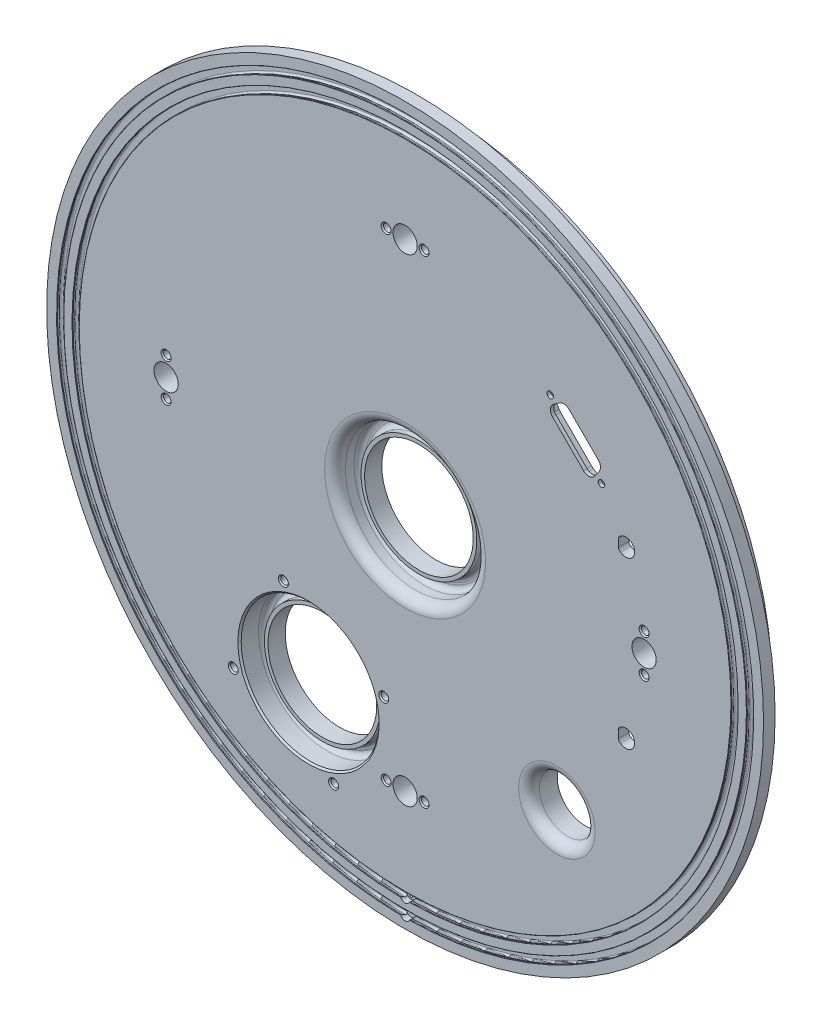
SolidWorks part; units mm, degrees
ref_plane "Front Plane" through (0, 0, 0) normal (0, 0, 1) x (1, 0, 0)
ref_plane "Top Plane" through (0, 0, 0) normal (0, 1, 0) x (1, 0, 0)
ref_plane "Right Plane" through (0, 0, 0) normal (1, 0, 0) x (0, 0, -1)
ref_axis "Axis1" through (0, 0, 87.1104) along (0, 0, -1)
sketch "Sketch1" plane through (0, 0, 0) normal (0, 0, 1) x (1, 0, 0)
  line L0 (-16.4103, -32.8206) -> (-28.0584, -56.1169) construction
  line L1 (-165.1, 165.1) -> (165.1, 165.1)
  line L2 (-165.1, 165.1) -> (-165.1, -165.1)
  line L3 (-165.1, -165.1) -> (165.1, -165.1)
  line L4 (165.1, 165.1) -> (165.1, -165.1)
  line L5 (0, -44.2246) -> (0, -100.8465) construction
  circle A0 centre (-44.45, -88.9) radius 25.4 construction
  circle A1 centre (0, 0) radius 25.4 construction
  circle A2 centre (69.85, -82.55) radius 11.7272 construction
  point P4 (165.1, 0)
  point P5 (0, 165.1)
  dimension "D3" = 50.8
  dimension "D4" = 50.8
  dimension "D5" = 44.45
  dimension "D9" = 69.85
  dimension "D1" = 330.2
  dimension "D2" = 330.2
  dimension "D6" = 88.9
  dimension "D7" = 26.565
  dimension "D8" = 82.55
extrude "BE-00 Material Blank" add sketch "Sketch1" against normal blind 15.875 and the other way blind 0.508
ref_plane "Plane1" through (-44.45, 0, 0) normal (1, 0, 0) x (0, 0, -1)
ref_plane "Plane2" through (69.85, 0, 0) normal (1, 0, 0) x (0, 0, -1)
sketch "Sketch5" plane through (0, 0, 0) normal (1, 0, 0) x (0, 0, -1)
  line L0 (0, 164.973) -> (0, 23.8125)
  line L1 (0, 23.8125) -> (14.3002, 23.8125)
  line L2 (-26.7351, 0) -> (-26.7351, 307.1876)
  line L3 (-26.7351, 307.1876) -> (49.4649, 307.1876)
  line L4 (49.4649, 307.1876) -> (49.4649, 0)
  line L5 (14.3002, 154.7876) -> (8.9662, 154.7876)
  line L6 (7.366, 156.3878) -> (7.366, 157.3895)
  line L7 (7.366, 157.3895) -> (5.334, 164.973)
  line L8 (5.334, 164.973) -> (0, 164.973)
  line L9 (60.1954, 0) -> (97.9061, 0) construction
  line L10 (14.3002, 154.7876) -> (14.3002, 23.8125)
  line L11 (-26.7351, 0) -> (49.4649, 0)
  arc A0 (8.9662, 154.7876) -> (7.366, 156.3878) centre (8.9662, 156.3878) cw
  dimension "D8" = 1.6002
  dimension "D1" = 15
  dimension "D2" = 7.366
  dimension "D3" = 5.334
  dimension "D4" = 309.5752
  dimension "D5" = 329.946
  dimension "D6" = 152.4
  dimension "D7" = 47.625
  dimension "D9" = 76.2
  dimension "D10" = 14.3002
revolve "CR-00 Profile Turn All" cut sketch "Sketch5" angle 360 about L9
sketch "Sketch18" plane through (0, 0, 0) normal (1, 0, 0) x (0, 0, -1)
  line L0 (-0.0254, 171.45) -> (-0.0254, 160.528)
  line L1 (-0.0254, 171.45) -> (-19.0148, 171.45)
  line L2 (-19.0148, 171.45) -> (-19.0148, 119.9486)
  line L3 (-19.0148, 119.9486) -> (-0.0254, 138.938)
  line L4 (0.3319, 160.296) -> (1.7371, 160.9216)
  line L5 (2.8448, 160.2023) -> (2.8448, 157.2977)
  line L6 (0.3319, 157.204) -> (1.7371, 156.5784)
  line L7 (-0.0254, 156.972) -> (-0.0254, 153.416)
  line L8 (0.3319, 153.184) -> (1.7371, 153.8096)
  line L9 (2.8448, 153.0903) -> (2.8448, 150.1857)
  line L10 (0.3319, 150.092) -> (1.7371, 149.4664)
  line L11 (-0.0254, 149.86) -> (-0.0254, 138.938)
  line L12 (2.8448, 158.75) -> (4.383, 158.75) construction
  line L13 (2.8448, 151.638) -> (4.383, 151.638) construction
  line L14 (0, 164.973) -> (0, 23.8125) construction
  line L15 (-94.6502, 0) -> (-55.4542, 0) construction
  arc A0 (-0.0254, 160.528) -> (0.3319, 160.296) centre (0.2286, 160.528) ccw
  arc A1 (2.8448, 160.2023) -> (1.7371, 160.9216) centre (2.0574, 160.2023) ccw
  arc A2 (2.8448, 157.2977) -> (1.7371, 156.5784) centre (2.0574, 157.2977) cw
  arc A3 (-0.0254, 156.972) -> (0.3319, 157.204) centre (0.2286, 156.972) cw
  arc A4 (-0.0254, 153.416) -> (0.3319, 153.184) centre (0.2286, 153.416) ccw
  arc A5 (2.8448, 153.0903) -> (1.7371, 153.8096) centre (2.0574, 153.0903) ccw
  arc A6 (2.8448, 150.1857) -> (1.7371, 149.4664) centre (2.0574, 150.1857) cw
  arc A7 (-0.0254, 149.86) -> (0.3319, 150.092) centre (0.2286, 149.86) cw
  point P37 (-0.0254, 160.1369)
  point P38 (-0.0254, 157.3631)
  point P39 (-0.0254, 145)
  dimension "D4" = 3.048
  dimension "D9" = 0.7874
  dimension "D10" = 0.254
  dimension "D14" = 4.4794
  dimension "D1" = 45
  dimension "D2" = 24
  dimension "D3" = 0.0254
  dimension "D5" = 7.112
  dimension "D6" = 12.7
  dimension "D7" = 12.7
  dimension "D8" = 18.9894
  dimension "D11" = 2.8448
  dimension "D12" = 317.5
  dimension "D13" = 2.7737
  dimension "D15" = 290
  dimension "D16" = 300.1841
revolve "CR-00 O-ring Grooves Radome" cut sketch "Sketch18" angle 360 about axis through (0, 0, 87.1104) along (0, 0, -1)
sketch "Sketch51" plane through (0, 0, 0) normal (0, 0, 1) x (1, 0, 0)
  circle A0 centre (0, -152.4) radius 2.1844
  circle A1 centre (0, -159.512) radius 2.1844
  dimension "D1" = 4.3688
  dimension "D2" = 159.512
  dimension "D3" = 7.112
extrude "Cut-Extrude6" cut sketch "Sketch51" against normal up to surface (2.8448 mm away) up to face at (153.0903, 0, -2.8448)
sketch "Sketch8" plane through (0, 0, 0) normal (0, 0, 1) x (1, 0, 0)
  circle A0 centre (-44.5452, -80.5824) radius 23.8125
  circle A1 centre (88.9, -44.45) radius 7.9375
  circle A2 centre (-88.9, -50.8) radius 11.1125
  dimension "D1" = 47.625
  dimension "D2" = 15.875
  dimension "D3" = 22.225
  dimension "D4" = 92.075
  dimension "D5" = 44.45
  dimension "D6" = 50.8
  dimension "D7" = 88.9
  dimension "D8" = 88.9
extrude "CE-00 Holes Vacuum Fittings" [suppressed] cut sketch "Sketch8" against normal through all
hole_wizard "1/2 NPT Tapped Hole1" positions "Sketch3" profile "Sketch4" size "1/2" standard "Ansi Inch"
sketch "Sketch3" plane through (-58.3455, -97.3945, -18.542) normal (0, 0, 1) x (1, 0, 0)
  point P0 (58.3455, 97.3945)
sketch "Sketch4" plane through (0, 0, -18.542) normal (1, 0, 0) x (0, 1, 0)
  line L0 (0, 0) -> (0, 19.05)
  line L1 (0, 19.05) -> (8.9281, 19.05)
  line L2 (-10.2617, 13.5636) -> (-10.6678, 0) construction
  line L3 (8.9281, 19.05) -> (8.9281, 13.5636)
  line L4 (8.9281, 13.5636) -> (10.2617, 13.5636)
  line L5 (10.2617, 13.5636) -> (10.6678, 0)
  line L7 (10.6678, 0) -> (0, 0)
  line L8 (0, -6.35) -> (0, 107.95) construction
  line L11 (-8.9281, 13.5636) -> (-10.2617, 13.5636) construction
  dimension "Thru Tap Drill Dia." = 17.8562
  dimension "Thru Tap Drill Depth" = 19.05
  dimension "Thread Dia." = 21.3355
  dimension "Thread Angle" = 3.43
  dimension "Thread Depth" = 13.5636
hole_wizard "#10-32 Tapped Hole1" positions "Sketch7" profile "Sketch6" tap size "#10-32" standard "Ansi Inch"
sketch "Sketch7" plane through (20.4721, 110.2727, -18.034) normal (0, 0, -1) x (-1, 0, 0)
  point P0 (58.5721, -110.2727)
  dimension "D1" = 38.1
sketch "Sketch6" plane through (-38.1, 0, -18.034) normal (1, 0, 0) x (0, 1, 0)
  line L0 (0, 0) -> (0, 17.0883)
  line L1 (0, 17.0883) -> (2.0193, 15.875)
  line L2 (2.0193, 15.875) -> (2.0193, 0.5207)
  line L3 (2.0193, 0.5207) -> (2.54, 0)
  line L5 (2.54, 0) -> (0, 0)
  line L6 (-2.0193, 0.5207) -> (-2.54, 0) construction
  line L10 (0, 17.0883) -> (-2.0193, 15.875) construction
  line L11 (0, -6.35) -> (0, 107.95) construction
  dimension "Tap Drill Dia." = 4.0386
  dimension "Tap Drill Depth" = 15.875
  dimension "Near C'Sink Dia." = 5.08
  dimension "Near C'Sink Angle" = 90
  dimension "Drill Angle" = 118
pattern_circular "CirPattern1" [suppressed] count 6 over 360 about axis through (0, 0, 87.1104) along (0, 0, -1)
hole_wizard "#10-32 Tapped Hole2" positions "Sketch10" profile "Sketch9" tap size "#10-32" standard "Ansi Inch"
sketch "Sketch10" plane through (0, 0, -18.034) normal (0, 0, -1) x (-1, 0, 0)
  point P0 (82.6452, -80.5824)
  dimension "D1" = 38.1
sketch "Sketch9" plane through (-82.6452, -80.5824, -18.034) normal (1, 0, 0) x (0, 1, 0)
  line L0 (0, 0) -> (0, 17.0883)
  line L1 (0, 17.0883) -> (2.0193, 15.875)
  line L2 (2.0193, 15.875) -> (2.0193, 0.5207)
  line L3 (2.0193, 0.5207) -> (2.54, 0)
  line L5 (2.54, 0) -> (0, 0)
  line L6 (-2.0193, 0.5207) -> (-2.54, 0) construction
  line L10 (0, 17.0883) -> (-2.0193, 15.875) construction
  line L11 (0, -6.35) -> (0, 107.95) construction
  dimension "Tap Drill Dia." = 4.0386
  dimension "Tap Drill Depth" = 15.875
  dimension "Near C'Sink Dia." = 5.08
  dimension "Near C'Sink Angle" = 90
  dimension "Drill Angle" = 118
pattern_circular "CirPattern2" [suppressed] count 6 over 360
hole_wizard "#8-32 Tapped Hole1" positions "Sketch12" profile "Sketch11" tap size "#8-32" standard "Ansi Inch"
sketch "Sketch12" plane through (0, 0, -18.034) normal (0, 0, -1) x (-1, 0, 0)
  point P0 (88.9, -28.575)
  dimension "D1" = 22.225
sketch "Sketch11" plane through (-88.9, -28.575, -18.034) normal (1, 0, 0) x (0, 1, 0)
  line L0 (0, 0) -> (0, 16.9128)
  line L1 (0, 16.9128) -> (1.7272, 15.875)
  line L2 (1.7272, 15.875) -> (1.7272, 0.5588)
  line L3 (1.7272, 0.5588) -> (2.286, 0)
  line L5 (2.286, 0) -> (0, 0)
  line L6 (-1.7272, 0.5588) -> (-2.286, 0) construction
  line L10 (0, 16.9128) -> (-1.7272, 15.875) construction
  line L11 (0, -6.35) -> (0, 107.95) construction
  dimension "Tap Drill Dia." = 3.4544
  dimension "Tap Drill Depth" = 15.875
  dimension "Near C'Sink Dia." = 4.572
  dimension "Near C'Sink Angle" = 90
  dimension "Drill Angle" = 118
pattern_circular "CirPattern3" [suppressed] count 6 over 360
hole_wizard "#8-32 Tapped Hole2" positions "Sketch14" profile "Sketch13" tap size "#8-32" standard "Ansi Inch"
sketch "Sketch14" plane through (0, 0, -18.034) normal (0, 0, -1) x (-1, 0, 0)
  point P0 (-88.9, -22.225)
  dimension "D1" = 22.225
sketch "Sketch13" plane through (88.9, -22.225, -18.034) normal (1, 0, 0) x (0, 1, 0)
  line L0 (0, 0) -> (0, 16.9128)
  line L1 (0, 16.9128) -> (1.7272, 15.875)
  line L2 (1.7272, 15.875) -> (1.7272, 0.5588)
  line L3 (1.7272, 0.5588) -> (2.286, 0)
  line L5 (2.286, 0) -> (0, 0)
  line L6 (-1.7272, 0.5588) -> (-2.286, 0) construction
  line L10 (0, 16.9128) -> (-1.7272, 15.875) construction
  line L11 (0, -6.35) -> (0, 107.95) construction
  dimension "Tap Drill Dia." = 3.4544
  dimension "Tap Drill Depth" = 15.875
  dimension "Near C'Sink Dia." = 4.572
  dimension "Near C'Sink Angle" = 90
  dimension "Drill Angle" = 118
pattern_circular "CirPattern4" [suppressed] count 6 over 360
sketch "Sketch29" plane through (0, 0, -14.3002) normal (0, 0, -1) x (-1, 0, 0)
  line L0 (0, -50.1457) -> (0, -101.6575) construction
  line L1 (13.7482, 109.5375) -> (16.0393, 113.5059)
  line L2 (-13.7482, 109.5375) -> (-16.0393, 113.5059)
  line L3 (-122.2502, -22.225) -> (-122.2502, -50.6266)
  line L4 (36.6551, 106.0023) -> (26.1856, 46.6263)
  line L5 (-11.4874, -104.0576) -> (10.6367, -68.097)
  line L6 (102.2177, 9.9539) -> (117.5706, 15.5419)
  line L8 (122.2502, -22.225) -> (122.2502, -62.5112)
  line L9 (-120.3903, 53.7153) -> (-67.4739, 106.6317)
  line L10 (-122.2502, 49.2252) -> (-122.2502, 22.225)
  line L11 (-55.441, 102.8378) -> (-40.4593, 17.872)
  line L12 (-88.4934, -87.6335) -> (-66.2507, -55.8677) construction
  line L13 (-117.5706, -15.5419) -> (-102.2177, -9.9539)
  line L14 (-32.0892, -40.2927) -> (-46.5225, -60.9056)
  line L15 (-63.958, -52.5933) -> (-41.6374, -20.7163)
  line L16 (99.7853, -9.525) -> (47.4632, -9.525)
  line L17 (88.4934, -87.6335) -> (41.6374, -20.7163)
  line L18 (122.2502, 49.2252) -> (122.2502, 22.225)
  line L19 (-102.2177, 9.9539) -> (-117.5706, 15.5419)
  line L20 (55.441, 102.8378) -> (40.4593, 17.872)
  line L21 (47.4632, 9.525) -> (99.7853, 9.525)
  line L22 (120.3903, 53.7153) -> (67.4739, 106.6317)
  line L23 (-36.6551, 106.0023) -> (-26.1856, 46.6263)
  line L24 (46.6891, -44.5372) -> (66.9379, -73.4555) construction
  line L25 (-12.674, -115.738) -> (-8.313, -127.7197)
  line L29 (-99.7853, -9.525) -> (-47.4632, -9.525)
  line L30 (117.5706, -15.5419) -> (102.2177, -9.9539)
  line L31 (-47.4632, 9.525) -> (-99.7853, 9.525)
  arc A0 (10.6367, -68.097) -> (29.0762, -52.2974) centre (44.45, -88.9) cw
  arc A1 (-15.8102, -137.2174) -> (-46.3064, -130.1318) centre (0, 0) cw
  arc A2 (22.2264, -38.494) -> (-22.6409, -38.2517) centre (0, 0) cw
  arc A3 (122.2502, 49.2252) -> (120.3903, 53.7153) centre (115.9002, 49.2252) ccw
  arc A4 (-122.2502, 49.2252) -> (-120.3903, 53.7153) centre (-115.9002, 49.2252) cw
  arc A5 (55.441, 102.8378) -> (67.4739, 106.6317) centre (62.445, 101.6028) cw
  arc A6 (102.2177, 9.9539) -> (99.7853, 9.525) centre (99.7853, 16.637) cw
  arc A7 (40.4593, 17.872) -> (47.4632, 9.525) centre (47.4632, 16.637) ccw
  arc A8 (-22.6409, -38.2517) -> (-32.0892, -40.2927) centre (-26.2634, -44.372) ccw
  arc A9 (-8.313, -127.7197) -> (-15.8102, -137.2174) centre (-14.9961, -130.1521) cw
  arc A10 (-115.0213, -76.4765) -> (-109.4209, -84.2949) centre (0, 0) ccw
  arc A11 (121.3884, -65.9046) -> (106.1569, -88.3701) centre (0, 0) cw
  arc A12 (29.0762, -52.2974) -> (22.2264, -38.494) centre (26.0866, -45.1797) ccw
  arc A13 (47.4632, -9.525) -> (41.6374, -20.7163) centre (47.4632, -16.637) ccw
  arc A14 (-26.1856, 46.6263) -> (-16.5359, 41.2598) centre (-19.1816, 47.8613) ccw
  arc A15 (-16.0393, 113.5059) -> (-36.6551, 106.0023) centre (-25.6857, 107.9365) ccw
  arc A16 (16.0393, 113.5059) -> (36.6551, 106.0023) centre (25.6857, 107.9365) cw
  arc A17 (16.5359, 41.2598) -> (26.1856, 46.6263) centre (19.1816, 47.8613) ccw
  arc A18 (-40.4593, 17.872) -> (-47.4632, 9.525) centre (-47.4632, 16.637) cw
  arc A19 (122.2502, 22.225) -> (117.5706, 15.5419) centre (115.1382, 22.225) cw
  arc A20 (-55.441, 102.8378) -> (-67.4739, 106.6317) centre (-62.445, 101.6028) ccw
  arc A21 (-50.9341, -122.2424) -> (-46.3064, -130.1318) centre (-43.9221, -123.4314) ccw
  arc A22 (122.2502, -22.225) -> (117.5706, -15.5419) centre (115.1382, -22.225) ccw
  arc A23 (-52.9134, -103.4798) -> (-46.7884, -68.6552) centre (-69.85, -82.55) ccw
  arc A24 (-69.7976, -55.6261) -> (-96.6956, -80.4969) centre (-69.85, -82.55) ccw
  arc A25 (-102.2177, -9.9539) -> (-99.7853, -9.525) centre (-99.7853, -16.637) cw
  arc A26 (-117.2181, -57.4276) -> (-122.2502, -50.6266) centre (-115.1382, -50.6266) cw
  arc A27 (-114.3694, -67.7636) -> (-115.0213, -76.4765) centre (-109.099, -72.5388) ccw
  arc A28 (-52.9134, -103.4798) -> (-53.5204, -113.9849) centre (-48.4396, -109.0084) ccw
  arc A29 (-69.7976, -55.6261) -> (-63.958, -52.5933) centre (-69.7838, -48.5141) ccw
  arc A30 (16.5359, 41.2598) -> (-16.5359, 41.2598) centre (0, 0) ccw
  arc A31 (122.2502, -62.5112) -> (121.3884, -65.9046) centre (115.1382, -62.5112) cw
  arc A32 (106.1569, -88.3701) -> (88.4934, -87.6335) centre (97.6066, -81.2524) cw
  arc A33 (102.2177, -9.9539) -> (99.7853, -9.525) centre (99.7853, -16.637) ccw
  arc A34 (-122.2502, -22.225) -> (-117.5706, -15.5419) centre (-115.1382, -22.225) cw
  arc A35 (-122.2502, 22.225) -> (-117.5706, 15.5419) centre (-115.1382, 22.225) ccw
  arc A36 (-102.2177, 9.9539) -> (-99.7853, 9.525) centre (-99.7853, 16.637) ccw
  arc A37 (-46.5225, -60.9056) -> (-46.7884, -68.6552) centre (-40.6967, -64.9849) ccw
  arc A38 (-50.9341, -122.2424) -> (-53.5204, -113.9849) centre (-60.325, -120.65) ccw
  arc A39 (-47.4632, -9.525) -> (-41.6374, -20.7163) centre (-47.4632, -16.637) cw
  arc A40 (13.7482, 109.5375) -> (-13.7482, 109.5375) centre (0, 117.475) cw
  arc A41 (-11.4874, -104.0576) -> (-12.674, -115.738) centre (0, -111.125) ccw
  arc A42 (-114.3694, -67.7636) -> (-117.2181, -57.4276) centre (-119.0752, -63.5) ccw
  arc A43 (-109.4209, -84.2949) -> (-96.6956, -80.4969) centre (-103.7869, -79.9546) ccw
  circle A44 centre (44.45, -88.9) radius 38.4753 construction
  circle A48 centre (0, 0) radius 42.7686 construction
  dimension "D5" = 138.1252
  dimension "D6" = 11.1252
  dimension "D7" = 9.525
  dimension "D9" = 35
  dimension "D12" = 44.45
  dimension "D13" = 6.35
  dimension "D15" = 44.45
  dimension "D11" = 39.7002
  dimension "D19" = 7.112
  dimension "D22" = 49.2252
  dimension "D16" = 15.875
  dimension "D24" = 11.1387
  dimension "D28" = 13.4874
  dimension "D29" = 22.225
  dimension "D30" = 7.112
  dimension "D32" = 7.112
  dimension "D31" = 53.848
  dimension "D33" = 7.112
  dimension "D34" = 7.112
  dimension "D36" = 7.112
  dimension "D38" = 7.112
  dimension "D40" = 9.525
  dimension "D43" = 6.35
  dimension "D45" = 7.112
  dimension "D47" = 7.112
  dimension "D50" = 22.225
  dimension "D51" = 60
  dimension "D26" = 119.0752
  dimension "D4" = 122.2502
  dimension "D8" = 9.525
  dimension "D10" = 9.525
  dimension "D14" = 45
  dimension "D17" = 88.9
  dimension "D18" = 111.125
  dimension "D21" = 9.525
  dimension "D23" = 19.05
  dimension "D25" = 117.475
  dimension "D27" = 19.05
  dimension "D35" = 20
  dimension "D37" = 9.525
  dimension "D39" = 38.1
  dimension "D41" = 63.5
  dimension "D42" = 119.0752
  dimension "D44" = 20
  dimension "D46" = 22.225
  dimension "D48" = 80
  dimension "D49" = 20
extrude "Cut-Extrude4" cut sketch "Sketch29" against normal blind 9.525
sketch "Sketch15" plane through (0, 0, -14.3002) normal (0, 0, -1) x (-1, 0, 0)
  line L0 (-67.437, 18.288) -> (-84.963, -30.988) construction
  line L1 (-84.963, 25.4) -> (-67.437, 25.4)
  line L2 (-92.075, 18.288) -> (-92.075, -30.988)
  line L3 (-84.963, -38.1) -> (-67.437, -38.1)
  line L4 (-60.325, 18.288) -> (-60.325, -30.988)
  arc A0 (-92.075, -30.988) -> (-84.963, -38.1) centre (-84.963, -30.988) ccw
  arc A1 (-84.963, 25.4) -> (-92.075, 18.288) centre (-84.963, 18.288) ccw
  arc A2 (-67.437, 25.4) -> (-60.325, 18.288) centre (-67.437, 18.288) cw
  arc A3 (-67.437, -38.1) -> (-60.325, -30.988) centre (-67.437, -30.988) ccw
  point P12 (-76.2, -6.35)
  dimension "D1" = 7.112
  dimension "D2" = 6.35
  dimension "D3" = 76.2
  dimension "D4" = 31.75
  dimension "D5" = 63.5
extrude "CE-00 Connector Pocket Outboard" [suppressed] cut sketch "Sketch15" against normal offset from surface (11.1252 mm away) 3.175
hole_wizard "3/8-24 Tapped Hole1" positions "Sketch17" profile "Sketch16" tap size "3/8-24" standard "Ansi Inch"
sketch "Sketch17" plane through (0, 0, 0) normal (0, 0, 1) x (1, 0, 0)
  point P0 (38.1, 63.5)
  dimension "D1" = 38.1
  dimension "D2" = 63.5
sketch "Sketch16" plane through (38.1, 63.5, 0) normal (1, 0, 0) x (0, -1, 0)
  line L0 (0, 0) -> (0, 18.411)
  line L1 (0, 18.411) -> (4.2164, 15.8775)
  line L2 (4.2164, 15.8775) -> (4.2164, 0.8001)
  line L3 (4.2164, 0.8001) -> (5.0165, 0)
  line L5 (5.0165, 0) -> (0, 0)
  line L6 (-4.2164, 0.8001) -> (-5.0165, 0) construction
  line L10 (0, 18.411) -> (-4.2164, 15.8775) construction
  line L11 (0, -6.35) -> (0, 107.95) construction
  dimension "Tap Drill Dia." = 8.4328
  dimension "Tap Drill Depth" = 15.8775
  dimension "Near C'Sink Dia." = 10.033
  dimension "Near C'Sink Angle" = 90
  dimension "Drill Angle" = 118
sketch "Sketch34" plane through (0, 0, -14.3002) normal (0, 0, -1) x (-1, 0, 0)
  line L0 (-55.0645, 131.7752) -> (55.0645, 131.7752)
  line L1 (64.0447, 128.0555) -> (131.2305, 60.8697)
  line L2 (134.9502, 51.8895) -> (134.9502, -64.292)
  line L3 (0, 83.406) -> (0, 58.953) construction
  line L4 (-134.9502, 51.8895) -> (-134.9502, -64.292)
  line L5 (-64.0447, 128.0555) -> (-131.2305, 60.8697)
  line L6 (-55.0645, 124.6632) -> (55.0645, 124.6632)
  line L7 (59.0158, 123.0265) -> (126.2015, 55.8408)
  line L8 (127.8382, 51.8895) -> (127.8382, -64.292)
  line L9 (-127.8382, 51.8895) -> (-127.8382, -64.292)
  line L10 (-59.0158, 123.0265) -> (-126.2015, 55.8408)
  arc A0 (-133.4906, -70.2033) -> (133.4906, -70.2033) centre (0, 0) ccw
  arc A1 (55.0645, 131.7752) -> (64.0447, 128.0555) centre (55.0645, 119.0752) cw
  arc A2 (131.2305, 60.8697) -> (134.9502, 51.8895) centre (122.2502, 51.8895) cw
  arc A3 (134.9502, -64.292) -> (133.4906, -70.2033) centre (122.2502, -64.292) cw
  arc A4 (-134.9502, -64.292) -> (-133.4906, -70.2033) centre (-122.2502, -64.292) ccw
  arc A5 (-131.2305, 60.8697) -> (-134.9502, 51.8895) centre (-122.2502, 51.8895) ccw
  arc A6 (-55.0645, 131.7752) -> (-64.0447, 128.0555) centre (-55.0645, 119.0752) ccw
  arc A7 (55.0645, 124.6632) -> (59.0158, 123.0265) centre (55.0645, 119.0752) cw
  arc A8 (126.2015, 55.8408) -> (127.8382, 51.8895) centre (122.2502, 51.8895) cw
  arc A9 (127.8382, -64.292) -> (127.196, -66.893) centre (122.2502, -64.292) cw
  arc A10 (-127.196, -66.893) -> (127.196, -66.893) centre (0, 0) ccw
  arc A11 (-127.8382, -64.292) -> (-127.196, -66.893) centre (-122.2502, -64.292) ccw
  arc A12 (-126.2015, 55.8408) -> (-127.8382, 51.8895) centre (-122.2502, 51.8895) ccw
  arc A13 (-55.0645, 124.6632) -> (-59.0158, 123.0265) centre (-55.0645, 119.0752) ccw
  point P11 (134.9502, 57.15)
  dimension "D2" = 150.8252
  dimension "D6" = 12.7
  dimension "D1" = 134.9502
  dimension "D3" = 131.7752
  dimension "D4" = 45
  dimension "D5" = 57.15
  dimension "D7" = 7.112
extrude "CE-00 Groove for Gasket" cut sketch "Sketch34" against normal blind 2.286
sketch "Sketch23" plane through (0, 0, 0) normal (1, 0, 0) x (0, 0, -1)
  line L0 (44.6896, 25.019) -> (6.35, 25.019)
  line L1 (6.35, 25.019) -> (6.35, 26.67)
  line L2 (6.35, 26.67) -> (11.1252, 26.67)
  line L3 (11.1252, 26.67) -> (11.1252, 32.258)
  line L4 (11.1252, 32.258) -> (-9.343, 32.258)
  line L5 (-9.343, 32.258) -> (-9.343, 0)
  line L6 (-9.343, 0) -> (44.6896, 0)
  line L7 (44.6896, 0) -> (44.6896, 25.019)
  line L8 (44.6896, 0) -> (-27.2201, 0) construction
  dimension "D1" = 1.651
  dimension "D2" = 5.588
  dimension "D3" = 6.35
  dimension "D4" = 4.7752
  dimension "D5" = 50.038
revolve "CR-00 Hole for Cooler" cut sketch "Sketch23" angle 360 about L8
sketch "Sketch20" plane through (0, 0, 0) normal (0, 0, -1) x (-1, 0, 0)
  circle A0 centre (-109.982, 0) radius 5.588
  dimension "D1" = 11.176
  dimension "D2" = 109.982
extrude "CE-00 Standoff Pocket" cut sketch "Sketch20" along normal blind 11.43
hole_wizard "#8-32 Tapped Hole3" positions "Sketch22" profile "Sketch21" tap size "#8-32" standard "Ansi Inch"
sketch "Sketch22" plane through (-31.988, -4.2355, 0) normal (0, 0, -1) x (-1, 0, 0)
  point P0 (-141.97, 12.9731)
  point P1 (-141.97, -4.5021)
  dimension "D1" = 8.7376
  dimension "D2" = 8.7376
sketch "Sketch21" plane through (109.982, 8.7376, 0) normal (1, 0, 0) x (0, -1, 0)
  line L0 (0, 0) -> (0, 12.163)
  line L1 (0, 12.163) -> (1.7272, 11.1252)
  line L2 (1.7272, 11.1252) -> (1.7272, 0.5588)
  line L3 (1.7272, 0.5588) -> (2.286, 0)
  line L5 (2.286, 0) -> (0, 0)
  line L6 (-1.7272, 0.5588) -> (-2.286, 0) construction
  line L10 (0, 12.163) -> (-1.7272, 11.1252) construction
  line L11 (0, -6.35) -> (0, 107.95) construction
  dimension "Tap Drill Dia." = 3.4544
  dimension "Tap Drill Depth" = 11.1252
  dimension "Near C'Sink Dia." = 4.572
  dimension "Near C'Sink Angle" = 90
  dimension "Drill Angle" = 118
pattern_circular "CirPattern5" count 4 over 360 about axis through (0, 0, 0) along (0, 0, 1) of "CE-00 Standoff Pocket"
pattern_circular "CirPattern6" count 4 over 360 about axis through (0, 0, 0) along (0, 0, 1) of "#8-32 Tapped Hole3"
sketch "Sketch24" plane through (-44.45, 0, 0) normal (1, 0, 0) x (0, 0, -1)
  line L0 (30.0042, -63.881) -> (6.35, -63.881)
  line L1 (6.35, -63.881) -> (6.35, -62.23)
  line L2 (6.35, -62.23) -> (11.1252, -62.23)
  line L3 (11.1252, -62.23) -> (11.1252, -57.15)
  line L4 (11.1252, -57.15) -> (-16.0152, -57.15)
  line L5 (-16.0152, -57.15) -> (-16.0152, -88.9)
  line L6 (-16.0152, -88.9) -> (30.0042, -88.9)
  line L7 (30.0042, -88.9) -> (30.0042, -63.881)
  line L8 (30.0042, -88.9) -> (55.7967, -88.9) construction
  dimension "D1" = 4.7752
  dimension "D2" = 6.35
  dimension "D3" = 1.651
  dimension "D4" = 5.08
  dimension "D5" = 50.038
  dimension "D6" = 88.9
revolve "CR-00 Hole for Turbo" cut sketch "Sketch24" angle 360 about L8
hole_wizard "#8-32 Tapped Hole5" positions "Sketch36" profile "Sketch35" tap size "#8-32" standard "Ansi Inch"
sketch "Sketch36" plane through (0, 0, 0) normal (0, 0, 1) x (1, 0, 0)
  line L0 (-40.2898, -101.3805) -> (-36.1326, -113.8522)
  line L2 (-36.9993, -86.4164) -> (-27.3671, -83.2057)
  line L3 (-41.5014, -83.0027) -> (-35.3105, -70.6209)
  circle A0 centre (-44.45, -88.9) radius 36.5125 construction
  point P0 (-9.8112, -77.3537)
  point P1 (-55.9963, -54.2612)
  point P3 (-79.0888, -100.4463)
  point P5 (-32.9037, -123.5388)
  dimension "D1" = 73.025
  dimension "D2" = 45
sketch "Sketch35" plane through (-9.8112, -77.3537, 0) normal (1, 0, 0) x (0, -1, 0)
  line L0 (0, 0) -> (0, 12.163)
  line L1 (0, 12.163) -> (1.7272, 11.1252)
  line L2 (1.7272, 11.1252) -> (1.7272, 0.5588)
  line L3 (1.7272, 0.5588) -> (2.286, 0)
  line L5 (2.286, 0) -> (0, 0)
  line L6 (-1.7272, 0.5588) -> (-2.286, 0) construction
  line L10 (0, 12.163) -> (-1.7272, 11.1252) construction
  line L11 (0, -6.35) -> (0, 107.95) construction
  dimension "Tap Drill Dia." = 3.4544
  dimension "Tap Drill Depth" = 11.1252
  dimension "Near C'Sink Dia." = 4.572
  dimension "Near C'Sink Angle" = 90
  dimension "Drill Angle" = 118
sketch "Sketch28" plane through (0, 0, -4.7752) normal (0, 0, -1) x (-1, 0, 0)
  line L0 (-99.1959, 34.8549) -> (-98.685, 35.2334)
  line L1 (-98.171, -39.9461) -> (-98.171, -36.2539)
  line L2 (-98.685, -40.9666) -> (-99.1959, -41.3451)
  line L3 (-36.2198, 0) -> (-18.1078, 0) construction
  line L4 (-98.685, 40.9666) -> (-99.1959, 41.3451)
  line L5 (-98.171, 39.9461) -> (-98.171, 36.2539)
  line L6 (-99.1959, -34.8549) -> (-98.685, -35.2334)
  arc A0 (-98.685, 35.2334) -> (-98.171, 36.2539) centre (-99.441, 36.2539) ccw
  arc A1 (-98.171, 39.9461) -> (-98.685, 40.9666) centre (-99.441, 39.9461) ccw
  arc A2 (-99.1959, 41.3451) -> (-99.1959, 34.8549) centre (-101.6, 38.1) ccw
  arc A3 (-99.1959, -41.3451) -> (-99.1959, -34.8549) centre (-101.6, -38.1) cw
  arc A4 (-98.171, -39.9461) -> (-98.685, -40.9666) centre (-99.441, -39.9461) cw
  arc A5 (-98.685, -35.2334) -> (-98.171, -36.2539) centre (-99.441, -36.2539) cw
  point P12 (-98.171, 38.1)
  point P14 (-98.2282, 40.3228)
  point P23 (-98.2282, -40.3228)
  point P24 (-98.171, -38.1)
  dimension "D2" = 7.4676
  dimension "D7" = 8.0772
  dimension "D10" = 101.6
  dimension "D4" = 1.27
  dimension "D5" = 0.381
  dimension "D9" = 38.1
extrude "Cut-Extrude3 Connector Holes" cut sketch "Sketch28" against normal up to next
hole_wizard "5/16 (0.3125) Diameter Hole1" positions "Sketch26" profile "Sketch25" hole size "5/16" standard "Ansi Inch"
sketch "Sketch26" plane through (-38.4612, -65.1102, -4.7752) normal (0, 0, -1) x (-1, 0, 0)
  line L0 (-117.0385, 130.2171) -> (-103.5681, 143.6874) construction
  line L2 (-110.3033, 136.9522) -> (-33.6838, 60.3328) construction
  line L4 (-66.1766, 65.1102) -> (-45.0362, 65.1102) construction
  point P0 (-103.5681, 143.6874)
  point P1 (-117.0385, 130.2171)
  dimension "D1" = 45
  dimension "D2" = 101.6
  dimension "D3" = 19.05
sketch "Sketch25" plane through (65.1069, 78.5772, -4.7752) normal (1, 0, 0) x (0, 1, 0)
  line L0 (0, 0) -> (0, 4.7752)
  line L1 (0, 4.7752) -> (3.9688, 4.7752)
  line L2 (3.9688, 4.7752) -> (3.9687, 0)
  line L5 (3.9687, 0) -> (0, 0)
  line L11 (0, -6.35) -> (0, 107.95) construction
  dimension "Thru Hole Dia." = 7.9375
  dimension "Thru Hole Depth" = 4.7752
hole_wizard "#10-32 Tapped Hole3" positions "Sketch38" profile "Sketch37" tap size "#10-32" standard "Ansi Inch"
sketch "Sketch38" plane through (0, 0, -14.3002) normal (0, 0, -1) x (-1, 0, 0)
  line L0 (0, -50.6385) -> (0, -70.2839) construction
  point P1 (92.075, -98.425)
  point P3 (50.8, 115.9002)
  point P5 (-50.8, 115.9002)
  point P7 (-60.325, -120.65)
  point P13 (119.0752, 11.1252)
  point P15 (-119.0752, 11.1252)
  point P20 (-119.0752, -63.5)
  point P22 (19.05, -134.9502)
  dimension "D1" = 115.9002
  dimension "D2" = 98.425
  dimension "D3" = 11.1252
  dimension "D4" = 92.075
  dimension "D5" = 119.0752
  dimension "D6" = 50.8
  dimension "D7" = 60.325
  dimension "D8" = 120.65
  dimension "D9" = 63.5
  dimension "D10" = 119.0752
  dimension "D11" = 19.05
  dimension "D12" = 134.9502
sketch "Sketch37" plane through (-92.075, -98.425, -14.3002) normal (1, 0, 0) x (0, 1, 0)
  line L0 (0, 0) -> (0, 13.2529)
  line L1 (0, 13.2529) -> (2.0193, 12.0396)
  line L2 (2.0193, 12.0396) -> (2.0193, 0.5207)
  line L3 (2.0193, 0.5207) -> (2.54, 0)
  line L5 (2.54, 0) -> (0, 0)
  line L6 (-2.0193, 0.5207) -> (-2.54, 0) construction
  line L10 (0, 13.2529) -> (-2.0193, 12.0396) construction
  line L11 (0, -6.35) -> (0, 107.95) construction
  dimension "Tap Drill Dia." = 4.0386
  dimension "Tap Drill Depth" = 12.0396
  dimension "Near C'Sink Dia." = 5.08
  dimension "Near C'Sink Angle" = 90
  dimension "Drill Angle" = 118
hole_wizard "#55 (0.052) Diameter Hole1" positions "Sketch40" profile "Sketch39" hole size "#55" standard "Ansi Inch"
sketch "Sketch40" plane through (0, 0, 0) normal (0, 0, 1) x (1, 0, 0)
  point P0 (0, -153.162)
  dimension "D1" = 153.162
sketch "Sketch39" plane through (0, -153.162, 0) normal (1, 0, 0) x (0, -1, 0)
  line L0 (0, 0) -> (0, 8.347)
  line L1 (0, 8.347) -> (0.6604, 7.9502)
  line L2 (0.6604, 7.9502) -> (0.6604, 0)
  line L5 (0.6604, 0) -> (0, 0)
  line L10 (0, 8.347) -> (-0.6604, 7.9502) construction
  line L11 (0, -6.35) -> (0, 107.95) construction
  dimension "Hole Dia." = 1.3208
  dimension "Hole Depth" = 7.9502
  dimension "Drill Angle" = 118
sketch "Sketch63" plane through (0, 0, 0) normal (1, 0, 0) x (0, 0, -1)
  line L0 (12.446, -189.4881) -> (12.446, -211.7501) construction
  line L1 (6.096, -154.7368) -> (12.446, -154.7368)
  line L2 (6.096, -154.7368) -> (6.096, -189.4881)
  line L3 (6.096, -189.4881) -> (12.446, -189.4881)
  line L4 (12.446, -154.7368) -> (12.446, -189.4881)
  point P4 (14.3002, -154.7876)
  dimension "D1" = 12.7
  dimension "D2" = 6.096
  dimension "D3" = 0.0508
revolve "Cut-Revolve2" cut sketch "Sketch63" angle 360 about L0
hole_wizard "#41 (0.096) Diameter Hole1" positions "Sketch65" profile "Sketch64" hole size "#41" standard "Ansi Inch"
sketch "Sketch65" plane through (0, -154.7368, 0) normal (0, -1, 0) x (1, 0, 0)
  point P0 (0, -8.89)
  dimension "D1" = 8.89
sketch "Sketch64" plane through (0, -154.7368, -8.89) normal (1, 0, 0) x (0, 0, -1)
  line L0 (0, 0) -> (0, 19.7826)
  line L1 (0, 19.7826) -> (1.2192, 19.05)
  line L2 (1.2192, 19.05) -> (1.2192, 0)
  line L5 (1.2192, 0) -> (0, 0)
  line L10 (0, 19.7826) -> (-1.2192, 19.05) construction
  line L11 (0, -6.35) -> (0, 107.95) construction
  dimension "Hole Dia." = 2.4384
  dimension "Hole Depth" = 19.05
  dimension "Drill Angle" = 118
hole_wizard "#10-32 Tapped Hole4" positions "Sketch43" profile "Sketch42" tap size "#10-32" standard "Ansi Inch"
sketch "Sketch43" plane through (0, 0, -14.3002) normal (0, 0, -1) x (-1, 0, 0)
  point P0 (0, -134.9502)
  dimension "D1" = 134.9502
sketch "Sketch42" plane through (0, -134.9502, -14.3002) normal (1, 0, 0) x (0, 1, 0)
  line L0 (0, 0) -> (0, 9.9509)
  line L1 (0, 9.9509) -> (2.0193, 8.7376)
  line L2 (2.0193, 8.7376) -> (2.0193, 0.635)
  line L3 (2.0193, 0.635) -> (2.6543, 0)
  line L5 (2.6543, 0) -> (0, 0)
  line L6 (-2.0193, 0.635) -> (-2.6543, 0) construction
  line L10 (0, 9.9509) -> (-2.0193, 8.7376) construction
  line L11 (0, -6.35) -> (0, 107.95) construction
  dimension "Tap Drill Dia." = 4.0386
  dimension "Tap Drill Depth" = 8.7376
  dimension "Near C'Sink Dia." = 5.3086
  dimension "Near C'Sink Angle" = 90
  dimension "Drill Angle" = 118
hole_wizard "3/16 (0.1875) Diameter Hole1" positions "Sketch45" profile "Sketch44" hole size "3/16" standard "Ansi Inch"
sketch "Sketch45" plane through (0, 0, 0) normal (0, 0, 1) x (1, 0, 0)
  point P0 (130.9086, -25.4)
  dimension "D1" = 133.35
  dimension "D2" = 25.4
sketch "Sketch44" plane through (130.9086, -25.4, 0) normal (1, 0, 0) x (0, -1, 0)
  line L0 (0, 0) -> (0, 12.556)
  line L1 (0, 12.556) -> (2.3812, 11.1252)
  line L2 (2.3812, 11.1252) -> (2.3812, 0)
  line L5 (2.3812, 0) -> (0, 0)
  line L10 (0, 12.556) -> (-2.3813, 11.1252) construction
  line L11 (0, -6.35) -> (0, 107.95) construction
  dimension "Hole Dia." = 4.7625
  dimension "Hole Depth" = 11.1252
  dimension "Drill Angle" = 118
pattern_circular "CirPattern7" [suppressed] count 4 over 360 about axis through (0, 0, 87.1104) along (0, 0, -1)
sketch "Sketch46" plane through (69.85, 0, 0) normal (1, 0, 0) x (0, 0, -1)
  line L0 (-25.4, -82.55) -> (25.4, -82.55)
  line L1 (25.4, -82.55) -> (25.4, -66.04)
  line L2 (13.0302, -69.723) -> (-6.35, -69.723)
  line L3 (-6.35, -69.723) -> (-6.35, -68.072)
  line L4 (-6.35, -68.072) -> (-3.175, -68.072)
  line L5 (-3.175, -68.072) -> (-3.175, -62.992)
  line L6 (-3.175, -62.992) -> (-25.4, -62.992)
  line L7 (-25.4, -62.992) -> (-25.4, -82.55)
  line L8 (12.7407, -66.04) -> (13.6652, -68.58)
  line L9 (25.4, -82.55) -> (59.121, -82.55) construction
  line L10 (13.6652, -68.58) -> (13.0302, -68.58)
  line L11 (13.0302, -68.58) -> (13.0302, -69.723)
  line L12 (12.7407, -66.04) -> (25.4, -66.04)
  point P9 (14.3002, -66.04)
  dimension "D1" = 25.654
  dimension "D2" = 5.08
  dimension "D3" = 1.651
  dimension "D4" = 25.4
  dimension "D5" = 25.4
  dimension "D6" = 3.175
  dimension "D7" = 6.35
  dimension "D8" = 70
  dimension "D9" = 14.3002
  dimension "D10" = 0.635
  dimension "D11" = 1.27
  dimension "D12" = 33.02
  dimension "D13" = 27.94
revolve "Cut-Revolve1" cut sketch "Sketch46" angle 360 about L9
fillet "Fillet1" radius 2.3876 4 edges at (-17.78, -88.9, -11.1252) (-12.7, -88.9, -11.1252) (-26.67, 0, -11.1252) (-32.258, 0, -11.1252)
hole_wizard "1/4-28 Tapped Hole1" positions "Sketch49" profile "Sketch48" tap size "1/4-28" standard "Ansi Inch"
sketch "Sketch49" plane through (0, 0, -14.3002) normal (0, 0, -1) x (-1, 0, 0)
  line L0 (-71.2675, -82.55) -> (-61.6419, -82.55)
  line L2 (-68.8477, -81.5477) -> (-62.0414, -74.7414)
  circle A0 centre (-69.85, -82.55) radius 1.4175 construction
  point P0 (-55.2571, -67.9571)
  dimension "D1" = 45
  dimension "D2" = 20.6375
sketch "Sketch48" plane through (55.2571, -67.9571, -14.3002) normal (1, 0, 0) x (0, 1, 0)
  line L0 (0, 0) -> (0, 12.7506)
  line L1 (0, 12.7506) -> (2.7051, 11.1252)
  line L2 (2.7051, 11.1252) -> (2.7051, 0.6731)
  line L3 (2.7051, 0.6731) -> (3.3782, 0)
  line L5 (3.3782, 0) -> (0, 0)
  line L6 (-2.7051, 0.6731) -> (-3.3782, 0) construction
  line L10 (0, 12.7506) -> (-2.7051, 11.1252) construction
  line L11 (0, -6.35) -> (0, 107.95) construction
  dimension "Tap Drill Dia." = 5.4102
  dimension "Tap Drill Depth" = 11.1252
  dimension "Near C'Sink Dia." = 6.7564
  dimension "Near C'Sink Angle" = 90
  dimension "Drill Angle" = 118
pattern_circular "CirPattern8" count 4 over 360 about axis through (69.85, -82.55, 0) along (0, 0, 1) of "1/4-28 Tapped Hole1"
sketch "Sketch50" plane through (0, 0, -14.3002) normal (0, 0, -1) x (-1, 0, 0)
  circle A0 centre (0, 0) radius 166.6875
  dimension "D1" = 333.375
chamfer "Chamfer1" distance 0.762 angle 45 1 edges at (-76.2, -88.9, 0)
fillet "Fillet2" radius 1.6002 69 edges at (-33.002, -41.7479, -4.7752) (-18.6188, -58.7527, -4.7752) (0.4254, -86.0773, -4.7752) (13.4183, -109.7619, -4.7752) (10.4935, -121.7288, -4.7752) (9.4137, -134.5587, -4.7752) (31.2597, -134.5414, -4.7752) (50.0567, -127.0297, -4.7752) (51.2354, -117.803, -4.7752) (55.5398, -108.5981, -4.7752) (43.333, -87.2139, -4.7752) (47.8045, -64.741, -4.7752) (39.3059, -50.5991, -4.7752) (27.7651, -37.4203, -4.7752) (-120.964, -18.1457, -4.7752) (-122.2502, -42.3681, -4.7752) (-122.0314, -64.2618, -4.7752) (-114.3258, -77.5124, -4.7752) (-97.1431, -92.3679, -4.7752) (-65.0654, -54.1749, -4.7752) (-41.1548, -13.353, -4.7752) (-42.0151, 12.0655, -4.7752) (-47.9501, 60.3549, -4.7752) (-60.3064, 108.3856, -4.7752) (-93.9321, 80.1735, -4.7752) (-121.7668, 51.6552, -4.7752) (-122.2502, 35.7251, -4.7752) (-120.964, 18.1457, -4.7752) (22.6383, 41.6459, -4.7752) (31.4203, 76.3143, -4.7752) (29.4953, 118.4035, -4.7752) (14.8937, 111.5217, -4.7752) (0, 101.6, -4.7752) (-14.8937, 111.5217, -4.7752) (-29.4953, 118.4035, -4.7752) (-31.4203, 76.3143, -4.7752) (-22.6383, 41.6459, -4.7752) (122.2502, 35.7251, -4.7752) (121.7668, 51.6552, -4.7752) (93.9321, 80.1735, -4.7752) (60.3064, 108.3856, -4.7752) (47.9501, 60.3549, -4.7752) (42.0151, 12.0655, -4.7752) (41.1548, -13.353, -4.7752) (52.7977, -36.6548, -4.7752) (66.506, -54.8257, -4.7752) (88.1287, -62.7815, -4.7752) (101.7529, -86.7695, -4.7752) (112.2892, -80.4345, -4.7752) (116.1911, -72.0081, -4.7752) (112.9535, -61.8128, -4.7752) (120.8554, -54.8567, -4.7752) (122.2502, -36.4258, -4.7752) (0.2401, -44.4494, -4.7752) (-73.6243, -9.525, -4.7752) (-73.6243, 9.525, -4.7752) (0, 44.45, -4.7752) (-101.0203, -9.633, -4.7752) (-109.8942, -12.7479, -4.7752) (-109.8942, 12.7479, -4.7752) (-101.0203, 9.633, -4.7752) (73.6243, 9.525, -4.7752) (101.0203, 9.633, -4.7752) (109.8942, 12.7479, -4.7752) (120.964, 18.1457, -4.7752) (120.964, -18.1457, -4.7752) (109.8942, -12.7479, -4.7752) (101.0203, -9.633, -4.7752) (73.6243, -9.525, -4.7752)
fillet "Fillet3" [suppressed] radius 1.6002
fillet "Fillet4" [suppressed] radius 1.6002
fillet "Fillet5" radius 4.7752 2 edges at (57.023, -82.55, 0) (-32.258, 0, 0)
sketch "Sketch52" plane through (0, 0, -4.7752) normal (0, 0, -1) x (-1, 0, 0)
  line L0 (-66.7862, 81.3881) -> (-90.3683, 57.8059) construction
  line L1 (-78.5772, 69.597) -> (-66.7862, 57.8059) construction
  line L2 (-82.1065, 58.8476) -> (-67.8279, 73.1262)
  line L3 (-68.2858, 78.3598) -> (-71.0746, 80.3125)
  line L4 (-75.466, 79.9283) -> (-88.9086, 66.4858)
  line L5 (-87.34, 59.3055) -> (-89.2928, 62.0943)
  line L6 (-66.7862, 57.8059) -> (-90.3683, 57.8059) construction
  arc A0 (-67.8279, 73.1262) -> (-68.2858, 78.3598) centre (-70.2525, 75.5509) ccw
  arc A1 (-71.0746, 80.3125) -> (-75.466, 79.9283) centre (-73.0414, 77.5036) ccw
  arc A2 (-89.2928, 62.0943) -> (-88.9086, 66.4858) centre (-86.4839, 64.0611) cw
  arc A3 (-82.1065, 58.8476) -> (-87.34, 59.3055) centre (-84.5312, 61.2723) cw
  circle A4 centre (-66.7862, 81.3881) radius 1.4986
  circle A5 centre (-90.3683, 57.8059) radius 1.4986
  dimension "D2" = 3.429
  dimension "D4" = 25.8686
  dimension "D10" = 2.9972
  dimension "D11" = 27.051
  dimension "D1" = 10.2108
  dimension "D3" = 100
  dimension "D5" = 5.1054
  dimension "D6" = 33.3502
  dimension "D7" = 45
  dimension "D8" = 6.35
  dimension "D9" = 104.775
extrude "Cut-Extrude7" cut sketch "Sketch52" against normal through all
sketch "Sketch53" plane through (0, 0, -4.7752) normal (0, 0, -1) x (-1, 0, 0)
  line L0 (-76.5257, 80.988) -> (-89.9682, 67.5454)
  line L1 (-66.7862, 57.8059) -> (-62.4904, 53.5101) construction
  line L2 (-81.0468, 57.7879) -> (-66.7682, 72.0666)
  line L3 (-66.0733, 72.9404) -> (-62.4776, 78.6968)
  line L4 (-69.5549, 85.6473) -> (-75.727, 81.6351)
  line L5 (-78.5772, 69.597) -> (-66.7862, 57.8059) construction
  line L6 (-94.6275, 60.5746) -> (-90.6153, 66.7467)
  line L7 (-81.9206, 57.093) -> (-87.6771, 53.4974)
  arc A0 (-66.7682, 72.0666) -> (-66.0733, 72.9404) centre (-70.2525, 75.5509) ccw
  arc A1 (-62.4776, 78.6968) -> (-69.5549, 85.6473) centre (-66.7862, 81.3881) ccw
  arc A2 (-75.727, 81.6351) -> (-76.5257, 80.988) centre (-73.0414, 77.5036) ccw
  arc A3 (-87.6771, 53.4974) -> (-94.6275, 60.5746) centre (-90.3683, 57.8059) cw
  arc A4 (-81.0468, 57.7879) -> (-81.9206, 57.093) centre (-84.5312, 61.2723) cw
  arc A5 (-90.6153, 66.7467) -> (-89.9682, 67.5454) centre (-86.4839, 64.0611) cw
  dimension "D1" = 13.208
  dimension "D2" = 5.08
extrude "Cut-Extrude8" cut sketch "Sketch53" against normal offset from surface (3.175 mm away) 1.6002 up to face at (91.8669, 57.8059, 0)
sketch "Sketch54" [suppressed] plane through (0, 0, -14.3002) normal (0, 0, -1) x (-1, 0, 0)
  line L0 (0, 0) -> (-69.85, -82.55)
sketch "Sketch56" [suppressed] plane through (0, 0, -4.3688) normal (0, 0, 1) x (1, 0, 0)
  circle A0 centre (0, 0) radius 161.6479 construction
  circle A1 centre (0, 0) radius 161.6479
sketch "Sketch57" [suppressed] plane through (0, 0, -4.3688) normal (0, 0, 1) x (1, 0, 0)
  circle A0 centre (0, 0) radius 155.8521 construction
  circle A1 centre (0, 0) radius 155.8521
sketch "Sketch58" [suppressed] plane through (0, 0, -4.3688) normal (0, 0, 1) x (1, 0, 0)
  circle A0 centre (0, 0) radius 146.2001 construction
  circle A1 centre (0, 0) radius 146.2001
sketch "Sketch59" [suppressed] plane through (0, 0, -4.3688) normal (0, 0, 1) x (1, 0, 0)
  circle A0 centre (0, 0) radius 151.9959 construction
  circle A1 centre (0, 0) radius 151.9959
sketch "Sketch60" [suppressed] plane through (0, 0, -6.35) normal (0, 0, 1) x (1, 0, 0)
  circle A0 centre (-44.45, -88.9) radius 31.75
  circle A1 centre (-44.45, -88.9) radius 31.75 construction
sketch "Sketch61" [suppressed] plane through (0, 0, -6.35) normal (0, 0, 1) x (1, 0, 0)
  circle A0 centre (0, 0) radius 32.258
  circle A1 centre (0, 0) radius 32.258 construction
sketch "Sketch62" [suppressed] plane through (0, 0, 0) normal (0, 0, 1) x (1, 0, 0)
  line L0 (0, 0) -> (0, -146.4942)
  line L1 (0, 0) -> (-44.45, -88.9)
  circle A0 centre (0, 0) radius 146.4942 construction
sketch "Sketch66" plane through (0, 0, -14.3002) normal (0, 0, -1) x (-1, 0, 0)
  line L0 (138.1252, -177.9304) -> (138.1252, 51.8895)
  line L1 (133.4755, 63.1148) -> (66.2898, 130.3005)
  line L2 (55.0645, 134.9502) -> (-55.0645, 134.9502)
  line L4 (0, 174.2258) -> (0, 242.1803) construction
  line L5 (-133.4755, 63.1148) -> (-66.2898, 130.3005)
  line L6 (-138.1252, -177.9304) -> (-138.1252, 51.8895)
  arc A0 (66.2898, 130.3005) -> (55.0645, 134.9502) centre (55.0645, 119.0752) ccw
  arc A1 (138.1252, 51.8895) -> (133.4755, 63.1148) centre (122.2502, 51.8895) ccw
  arc A2 (-66.2898, 130.3005) -> (-55.0645, 134.9502) centre (-55.0645, 119.0752) cw
  arc A3 (-138.1252, 51.8895) -> (-133.4755, 63.1148) centre (-122.2502, 51.8895) cw
  dimension "D2" = 138.1252
ref_plane "Plane3" [suppressed] through (-138.1252, -177.9304, -14.3002) normal (0, -1, 0) x (1, 0, 0)
sketch "Sketch67" [suppressed] plane through (3.175, -177.9304, 0) normal (0, 1, 0) x (1, 0, 0)
  line L0 (-138.7602, 14.9808) -> (-167.1144, 7.3833)
  line L1 (-167.2459, 7.366) -> (-176.8602, 7.366)
  line L2 (-176.8602, 7.366) -> (-176.8602, 14.9808)
  line L3 (-176.8602, 14.9808) -> (-138.7602, 14.9808)
  line L4 (154.2145, 7.366) -> (-160.5645, 7.366) construction
  arc A0 (-167.1144, 7.3833) -> (-167.2459, 7.366) centre (-167.2459, 7.874) cw
  dimension "D1" = 0.508
  dimension "D2" = 15
  dimension "D3" = 38.1
  dimension "D4" = 2.54
sweep "Cut-Sweep1" [suppressed] cut profiles "Sketch67" path "Sketch66"
sketch "Sketch68" plane through (0, 0, 0) normal (0, 0, 1) x (1, 0, 0)
  line L0 (-4.1451, -147.7605) -> (-1.4298, -152.4635)
  line L1 (1.4298, -152.4635) -> (4.1451, -147.7605)
  line L2 (4.1451, -147.7605) -> (-4.1451, -147.7605)
  arc A0 (-1.4298, -152.4635) -> (1.4298, -152.4635) centre (0, -151.638) ccw
  point P5 (0, -147.7605)
  dimension "D1" = 1.651
  dimension "D2" = 151.638
  dimension "D3" = 60
extrude "Cut-Extrude10" [suppressed] cut sketch "Sketch68" against normal offset from surface (4.1148 mm away) 0.254
sketch "Sketch69" [suppressed] plane through (0, 0, -14.3002) normal (0, 0, -1) x (-1, 0, 0)
  circle A0 centre (0, 0) radius 154.7876
  arc A1 (3.9653, -154.7368) -> (-3.9653, -154.7368) centre (0, 0) ccw construction
sketch "Sketch70" [suppressed] plane through (0, 0, -14.3002) normal (0, 0, -1) x (-1, 0, 0)
  circle A0 centre (-69.85, -82.55) radius 12.827
  circle A1 centre (-69.85, -82.55) radius 12.827 construction
sketch "Sketch71" [suppressed] plane through (0, 0, 0) normal (0, 0, 1) x (1, 0, 0)
  line L0 (0, 0) -> (-44.45, -88.9)
  line L1 (0, 109.982) -> (0, -109.982)
  line L2 (0, -109.982) -> (0, -151.638)
sketch "Sketch72" [suppressed] plane through (0, 0, 0) normal (0, 0, 1) x (1, 0, 0)
  circle A0 centre (0, -151.638) radius 0.6604
  circle A1 centre (0, -151.638) radius 0.6604 construction
sketch "Sketch73" plane through (0, 0, 0) normal (0, 0, 1) x (1, 0, 0)
  circle A0 centre (0, -153.162) radius 0.762
  circle A5 centre (0, -153.162) radius 0.6604 construction
sketch "Sketch74" plane through (0, 0, 0) normal (0, 0, 1) x (1, 0, 0)
  line L0 (0, 0) -> (0, -229.7069) construction
  line L1 (0, 0) -> (-198.188, 0) construction
sketch "Sketch75" plane through (0, 0, -14.3002) normal (0, 0, -1) x (-1, 0, 0)
  line L0 (0, -229.7069) -> (0, 194.2946) construction
  line L2 (198.188, 0) -> (-184.0999, 0) construction
